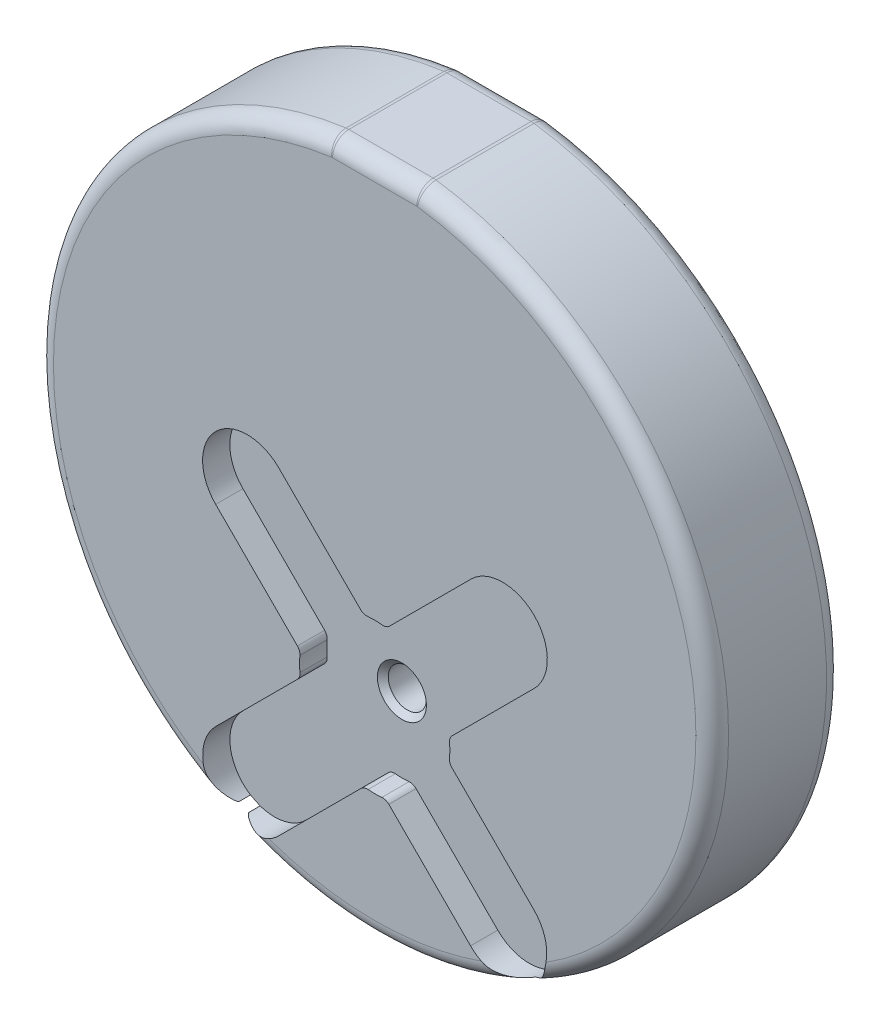
SolidWorks part; units mm, degrees
ref_plane "前视基准面" through (0, 0, 0) normal (0, 0, 1) x (1, 0, 0)
ref_plane "上视基准面" through (0, 0, 0) normal (0, 1, 0) x (1, 0, 0)
ref_plane "右视基准面" through (0, 0, 0) normal (1, 0, 0) x (0, 0, -1)
sketch "草图1" plane through (0, 0, 0) normal (0, 0, 1) x (1, 0, 0)
  line L0 (0, 35.6824) -> (0, -35.9959) construction
  line L1 (4, 30.7409) -> (-4, 30.7409)
  arc A0 (-4, 30.7409) -> (4, 30.7409) centre (0, 0) ccw
  point P8 (0, 30.7409)
  dimension "D1" = 62
  dimension "D2" = 8
extrude "凸台-拉伸1" add sketch "草图1" along normal blind 12 contours A0 L1
sketch "草图2" plane through (0, 0, 12) normal (0, 0, 1) x (1, 0, 0)
  line L0 (0, 32.9499) -> (0, -34.8565) construction
  circle A0 centre (0, -12.5) radius 1.75
  dimension "D1" = 3.5
  dimension "D2" = 12.5
extrude "切除-拉伸1" cut sketch "草图2" against normal through all
sketch "草图4" plane through (0, 0, 12) normal (0, 0, 1) x (1, 0, 0)
  line L0 (-5.9766, -12.5) -> (6.8579, -12.5) construction
  line L1 (0, -7.5543) -> (0, -18.1791) construction
  line L2 (14.6016, -21.3033) -> (6.8234, -13.5251)
  line L5 (8.8033, -27.1016) -> (1.0251, -19.3234)
  line L6 (16.272, -22.3104) -> (-14.9742, -3.4721) construction
  line L7 (-9.6877, 2.5324) -> (11.0999, -29.7236) construction
  line L8 (-14.5938, -21.3538) -> (-6.8156, -13.5756)
  line L11 (-8.7525, -27.109) -> (-0.9744, -19.3309)
  line L12 (-15.9099, -22.753) -> (15.9099, -2.247) construction
  line L13 (10.253, 3.4099) -> (-10.253, -28.4099) construction
  line L14 (1.0756, -5.6844) -> (8.8538, 2.0938)
  line L15 (-1.0251, -5.6766) -> (-8.8033, 2.1016)
  line L16 (-6.8234, -11.4749) -> (-14.6016, -3.6967)
  line L17 (6.8309, -11.5256) -> (14.609, -3.7475)
  line L18 (0, -12.5) -> (-14.6016, 2.1016) construction
  arc A0 (-8.8033, 2.1016) -> (-14.6016, -3.6967) centre (-11.7025, -0.7975) ccw
  arc A1 (-14.5938, -21.3538) -> (-8.7525, -27.109) centre (-11.6945, -24.2531) ccw
  arc A2 (8.8033, -27.1016) -> (14.6016, -21.3033) centre (11.7025, -24.2025) ccw
  arc A3 (14.609, -3.7475) -> (8.8538, 2.0938) centre (11.7531, -0.8055) ccw
  arc A4 (1.0756, -5.6844) -> (-1.0251, -5.6766) centre (0, -12.5) ccw
  arc A5 (-6.8234, -11.4749) -> (-6.8156, -13.5756) centre (0, -12.5) ccw
  arc A6 (-0.9744, -19.3309) -> (1.0251, -19.3234) centre (0, -12.5) ccw
  arc A7 (6.8234, -13.5251) -> (6.8309, -11.5256) centre (0, -12.5) ccw
  point P0 (0, -12.5)
  point P8 (0, -12.5)
  point P9 (0, -12.5)
  dimension "D7" = 13.8
  dimension "D1" = 8
  dimension "D2" = 8
  dimension "D3" = 37
  dimension "D4" = 37
  dimension "D5" = 45
  dimension "D6" = 45
  dimension "D8" = 11
  dimension "D9" = 8.2
  dimension "D10" = 12.2
  dimension "D11" = 8.2
extrude "切除-拉伸2" cut sketch "草图4" against normal blind 2.5
fillet "圆角2" radius 2 2 edges at (4, 30.7409, 6) (-4, 30.7409, 6)
fillet "圆角3" radius 1.5 9 edges at (-4.0019, 30.7364, 0) (0, 30.7409, 0) (4.0019, 30.7364, 0) (-4.0019, 30.7364, 12) (0, 30.7409, 12) (4.0019, 30.7364, 12) (0, -31, 0) (29.7614, -8.6751, 12) (-30.5756, 5.1122, 12)
fillet "圆角5" radius 0.8 8 edges at (-0.9744, -19.3309, 10.75) (1.0251, -19.3234, 10.75) (6.8234, -13.5251, 10.75) (6.8309, -11.5256, 10.75) (-6.8156, -13.5756, 10.75) (-6.8234, -11.4749, 10.75) (-1.0251, -5.6766, 10.75) (1.0756, -5.6844, 10.75)
chamfer "倒角2" distance 0.5 angle 45 2 edges at (1.75, -12.5, 9.5) (1.75, -12.5, 0)
